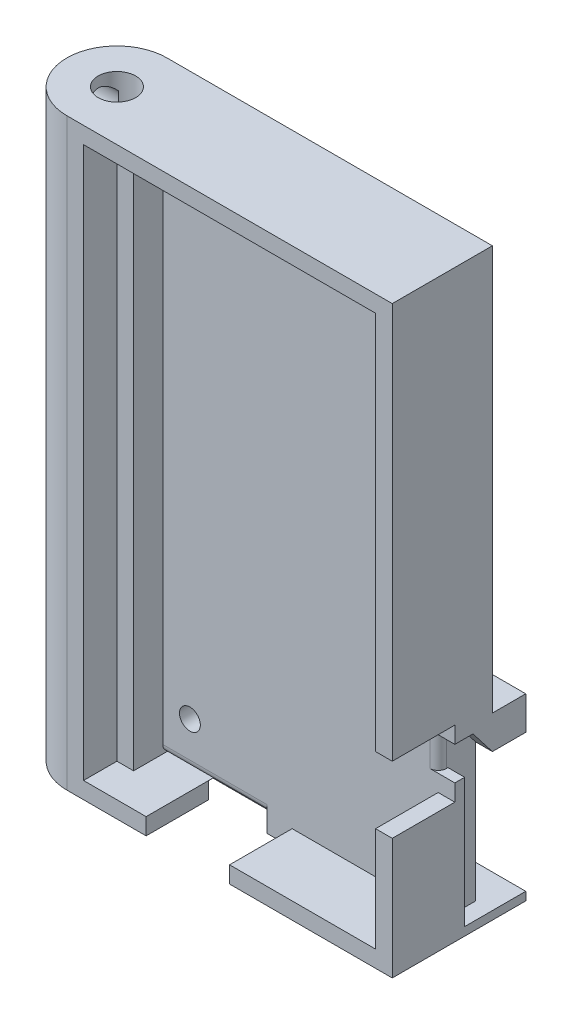
SolidWorks part; units mm, degrees
ref_plane "Front Plane" through (0, 0, 0) normal (0, 0, 1) x (1, 0, 0)
ref_plane "Top Plane" through (0, 0, 0) normal (0, 1, 0) x (1, 0, 0)
ref_plane "Right Plane" through (0, 0, 0) normal (1, 0, 0) x (0, 0, -1)
sketch "Sketch1" plane through (0, 0, 0) normal (0, 0, 1) x (1, 0, 0)
  line L1 (0, 0) -> (39, 0)
  line L2 (0, 0) -> (0, 70)
  line L3 (0, 70) -> (39, 70)
  line L4 (39, 0) -> (39, 70)
  dimension "D1" = 70
  dimension "D2" = 39
extrude "Base" add sketch "Sketch1" along normal blind 4.5
sketch "Sketch2" plane through (0, 0, 4.5) normal (0, 0, 1) x (1, 0, 0)
  line L0 (0, 70) -> (0, 0) construction
  line L1 (39, 70) -> (0, 70)
  line L2 (39, 70) -> (39, 66)
  line L3 (39, 66) -> (0, 66)
  line L4 (0, 70) -> (0, 66)
  line L5 (0, 0) -> (39, 0) construction
  line L6 (0, 66) -> (4, 66)
  line L7 (0, 66) -> (0, 0)
  line L8 (0, 0) -> (4, 0)
  line L9 (4, 66) -> (4, 0)
  line L10 (39, 0) -> (39, 70) construction
  line L11 (4, 0) -> (39, 0)
  line L12 (4, 0) -> (4, 4)
  line L13 (4, 4) -> (39, 4)
  line L14 (39, 0) -> (39, 4)
  line L16 (39, 66) -> (35, 66)
  line L17 (39, 66) -> (39, 4)
  line L18 (39, 4) -> (35, 4)
  line L19 (35, 66) -> (35, 4)
  line M6 (0, 70) -> (0, 0)
  line M7 (0, 0) -> (39, 0)
  line M8 (39, 0) -> (39, 70)
  line M9 (39, 70) -> (0, 70)
  dimension "D1" = 4
  dimension "D2" = 4
  dimension "D3" = 4
  dimension "D4" = 4
extrude "Walls" add sketch "Sketch2" along normal blind 7.5 contours L3 M8 M9 M6 | L3 L19 L13 M8 | L9 L3 M6 M7 | L13 L9 M7 M8 region at (19.5, 68, 4.5) region at (37, 35, 4.5) region at (2, 33, 4.5) region at (21.5, 2, 4.5)
sketch "Sketch3" plane through (0, 4, 0) normal (0, 1, 0) x (1, 0, 0)
  line L0 (4, -4.5) -> (35, -4.5) construction
  line L1 (9.5, -4.5) -> (19.5, -4.5)
  line L2 (9.5, -4.5) -> (9.5, -12)
  line L3 (9.5, -12) -> (19.5, -12)
  line L4 (19.5, -4.5) -> (19.5, -12)
  line L5 (4, -12) -> (35, -12) construction
  line L6 (4, -12) -> (4, -4.5) construction
  dimension "D1" = 5.5
  dimension "D2" = 15.5
extrude "PWR connector hole" cut sketch "Sketch3" against normal blind 4
sketch "Sketch4" plane through (35, 0, 0) normal (-1, 0, 0) x (0, 0, 1)
  line L0 (4.5, 66) -> (4.5, 4) construction
  line L1 (4.5, 14.5) -> (12, 14.5)
  line L2 (4.5, 14.5) -> (4.5, 22.5)
  line L3 (4.5, 22.5) -> (12, 22.5)
  line L4 (12, 14.5) -> (12, 22.5)
  line L5 (12, 66) -> (12, 4) construction
  line L6 (12, 4) -> (4.5, 4) construction
  dimension "D1" = 10.5
  dimension "D2" = 18.5
extrude "GPS connector hole" cut sketch "Sketch4" against normal blind 4
sketch "Sketch5" plane through (0, 0, 4.5) normal (0, 0, 1) x (1, 0, 0)
  line L0 (4, 4) -> (9.5, 4) construction
  line L1 (4, 66) -> (4, 4) construction
  line L2 (19.5, 66) -> (19.5, 4) construction
  line L3 (35, 66) -> (4, 66) construction
  line L5 (19.5, 35) -> (4, 35) construction
  line L6 (4, 66) -> (4, 4) construction
  circle A0 centre (7.25, 7.25) radius 1.25
  circle A1 centre (31.75, 7.25) radius 1.25
  circle A2 centre (7.25, 62.75) radius 1.25
  dimension "D1" = 3.25
  dimension "D3" = 2.5
  dimension "D2" = 3.25
extrude "Mounting holes" cut sketch "Sketch5" against normal blind 4
sketch "Sketch7" plane through (0, 0, 0) normal (0, 0, -1) x (-1, 0, 0)
  line L0 (-39, 0) -> (-39, 18.5) construction
  line L1 (-39, 0) -> (-39, 70) construction
  line L3 (-39, 1) -> (-8, 1)
  line L4 (-39, 1) -> (-39, 17.5)
  line L5 (-39, 17.5) -> (-8, 17.5)
  line L6 (-8, 1) -> (-8, 17.5)
  line L9 (0, 0) -> (-39, 0) construction
  line L10 (-39, 0) -> (-7, 0)
  line L11 (-7, 0) -> (-7, 18.5)
  line L12 (-7, 18.5) -> (-39, 18.5)
  line L13 (-39, 18.5) -> (-39, 17.5)
  line L14 (-39, 1) -> (-39, 0)
  line M8 (-39, 70) -> (-39, 0)
  line M9 (-39, 0) -> (0, 0)
  dimension "D1" = 18.5
  dimension "D2" = 1
  dimension "D3" = 16.5
  dimension "D4" = 31
  dimension "D5" = 32
  dimension "D6" = 18.5
extrude "GPS mount" add sketch "Sketch7" along normal blind 4 contours L11 L12 L5 L6 L3 M8 M9 region at (23.5, 0.6304, 0)
sketch "Sketch11" plane through (0, 0, 0) normal (0, 0, -1) x (-1, 0, 0)
  line L0 (0, 0) -> (-7, 0) construction
  line L1 (-3, 0) -> (-5, 0)
  line L2 (-3, 0) -> (-3, 21.5)
  line L3 (-3, 21.5) -> (-5, 21.5)
  line L4 (-5, 0) -> (-5, 21.5)
  line L5 (-7, 0) -> (-7, 18.5) construction
  line L7 (0, 70) -> (0, 0) construction
  line L8 (-5, 21.5) -> (-22, 21.5)
  line L9 (-5, 21.5) -> (-5, 20.5)
  line L10 (-5, 20.5) -> (-22, 20.5)
  line L11 (-22, 21.5) -> (-22, 20.5)
  line L12 (-7, 18.5) -> (-39, 18.5) construction
  line L13 (-39, 18.5) -> (-27, 18.5)
  line L14 (-39, 18.5) -> (-39, 21.5)
  line L15 (-39, 21.5) -> (-27, 21.5)
  line L16 (-27, 18.5) -> (-27, 21.5)
  line M5 (-7, 0) -> (0, 0)
  line M9 (-39, 18.5) -> (-7, 18.5)
  dimension "D1" = 2
  dimension "D2" = 2
  dimension "D3" = 21.5
  dimension "D4" = 1
  dimension "D5" = 22
  dimension "D6" = 5
  dimension "D7" = 12
  dimension "D8" = 3
extrude "PWR cable holder1" add sketch "Sketch11" along normal blind 4 contours L4 L2 L3 M5 | L8 L11 L10 L4 | L16 L15 L14 M9 region at (4, 10.75, 0) region at (13.5, 21, 0) region at (33, 20, 0)
sketch "Sketch12" plane through (0, 0, 0) normal (0, -1, 0) x (1, 0, 0)
  line L0 (19.5, 4.5) -> (9.5, 4.5) construction
  line L2 (5, 0) -> (5, 2)
  line L3 (5, 2) -> (16.5, 2)
  line L5 (9.5, 4.5) -> (9.5, 12) construction
  line L6 (9.5, 4.5) -> (16.5, 4.5)
  line L7 (9.5, 4.5) -> (9.5, 2)
  line L8 (9.5, 2) -> (16.5, 2)
  line L9 (16.5, 4.5) -> (16.5, 2)
  line L10 (19.5, 12) -> (19.5, 4.5) construction
  line L11 (5, 0) -> (7, 0)
  line L12 (5, 2) -> (9.5, 2)
  line L13 (5, 2) -> (5, 4.5)
  line L14 (5, 4.5) -> (9.5, 4.5)
  line L15 (9.5, 2) -> (9.5, 4.5)
  line L16 (7, 0) -> (7, 2)
  line M5 (19.5, 4.5) -> (9.5, 4.5)
  line M13 (5, 0) -> (7, 0)
  dimension "D1" = 2
  dimension "D2" = 0
  dimension "D3" = 3
  dimension "D4" = 11.5
fillet "PWR fillet2" radius 1 1 edges at (27, 21.5, -2)
fillet "PWR fillet3" radius 0.5 2 edges at (22, 21.5, -2) (22, 20.5, -2)
sketch "Sketch13" plane through (39, 0, 0) normal (1, 0, 0) x (0, 0, -1)
  line L0 (-4.5, 22.5) -> (-4.5, 14.5) construction
  line L1 (-4.5, 20.5) -> (-2.3266, 20.5)
  line L2 (-4.5, 20.5) -> (-4.5, 16.5)
  line L3 (-4.5, 16.5) -> (-2.3266, 16.5)
  line L4 (-2.3266, 20.5) -> (-2.3266, 16.5)
  line L5 (-12, 22.5) -> (-4.5, 22.5) construction
  line L6 (-4.5, 14.5) -> (-12, 14.5) construction
  line L7 (-2.3266, 16.5) -> (-2.3266, 11)
  line L8 (0, 1) -> (-2.3266, 1)
  line L9 (0, 1) -> (0, 11)
  line L10 (0, 11) -> (-2.3266, 11)
  line L11 (-2.3266, 1) -> (-2.3266, 11)
  line L16 (-2.3266, 20.5) -> (0, 17.5)
  line L17 (-2.3266, 16.5) -> (-3.3266, 16.5)
  line L22 (-2.3266, 16.5) -> (-2.3266, 1)
  line L23 (-2.3266, 1) -> (-3.3266, 1)
  line L24 (-3.3266, 16.5) -> (-3.3266, 1)
  line L25 (-2.3266, 11) -> (0, 11)
  line L26 (-2.3266, 11) -> (-2.3266, 17.5)
  line L27 (-2.3266, 17.5) -> (0, 17.5)
  line L28 (0, 11) -> (0, 17.5)
  line M19 (-4.5, 22.5) -> (-4.5, 14.5)
  line M27 (0, 1) -> (0, 17.5)
  dimension "D1" = 2
  dimension "D2" = 2
  dimension "D3" = 10
  dimension "D5" = 2.3266
  dimension "D6" = 1
sketch "Sketch15" plane through (0, 0, 0) normal (0, -1, 0) x (1, 0, 0)
  line L0 (0, 12) -> (0, 0) construction
  circle A0 centre (0, 6) radius 6
extrude "Ballon mount" add sketch "Sketch15" against normal blind 70
sketch "Sketch16" plane through (0, 0, 0) normal (0, -1, 0) x (1, 0, 0)
  line L0 (0, 0) -> (0, 6) construction
  circle A0 centre (0, 6) radius 2.25
  dimension "D1" = 4.5
extrude "Balloon mount hole" cut sketch "Sketch16" against normal blind 70
ref_plane "Plane1" through (-6, 0, 0) normal (-1, 0, 0) x (0, 0, 1)
sketch "Sketch21" plane through (-6, 0, 0) normal (-1, 0, 0) x (0, 0, 1)
  line L0 (6, 0) -> (6, 3.5) construction
  line L1 (0, 0) -> (12, 0) construction
  line L2 (0, 35) -> (12, 35) construction
  line L3 (0, 70) -> (0, 0) construction
  line L4 (12, 70) -> (12, 0) construction
  circle A0 centre (6, 3.5) radius 2.25
  circle A1 centre (6, 66.5) radius 2.25
  dimension "D2" = 4.5
  dimension "D1" = 3.5
extrude "Safety mount" cut sketch "Sketch21" against normal blind 4.5
sketch "Sketch22" plane through (0, 0, 12) normal (0, 0, 1) x (1, 0, 0)
  line L0 (19.5, 0) -> (39, 0) construction
  line L1 (2, 68) -> (37, 68)
  line L2 (2, 68) -> (2, 2)
  line L3 (2, 2) -> (37, 2)
  line L4 (37, 68) -> (37, 2)
  line L5 (39, 0) -> (39, 14.5) construction
  line L8 (39, 70) -> (0, 70) construction
  dimension "D1" = 35
  dimension "D2" = 2
  dimension "D3" = 2
  dimension "D4" = 2
extrude "Lid hole" cut sketch "Sketch22" against normal blind 7.5
sketch "Sketch25" plane through (2, 0, 0) normal (1, 0, 0) x (0, 0, -1)
  line L0 (-7.0308, 68) -> (-12, 68) construction
  line L1 (-4.5, 2) -> (-8, 2)
  line L2 (-4.5, 2) -> (-4.5, 68)
  line L3 (-4.5, 68) -> (-8, 68)
  line L4 (-8, 2) -> (-8, 68)
  dimension "D1" = 3.5
extrude "Correction" add sketch "Sketch25" along normal blind 2
fillet "Fillet4" radius 0.75 1 edges at (7, 18.5, -2)
fillet "Fillet5" radius 1 1 edges at (5, 20.5, -2)
extrude "Cut-Extrude2" cut sketch "Sketch12" against normal blind 1.99 contours L9 L7 L3 M5 | L14 L13 L3 L12 L7 | L16 L3 L2 M13 region at (6, 0, 1) region at (7.25, 0, 3.25) region at (13, 0, 3.25)
extrude "Cut-Extrude3" cut sketch "Sketch13" against normal blind 2 contours L4 L1 L3 M19 | L4 L27 L16 | L27 L4 L7 L10 M27 | L3 L24 L23 L11 L7 | L11 L8 L10 M27 region at (39, 18.5, 3.4133) region at (39, 18.5, 1.5511) region at (39, 14.25, 1.1633) region at (39, 8.75, 2.8266) region at (39, 6, 1.1633)
fillet "Fillet6" radius 1 1 edges at (37, 18.5, 4.5)
fillet "Fillet7" radius 1 1 edges at (6, 1.99, 0)
fillet "Fillet8" radius 1 1 edges at (13, 1.99, 4.5)
